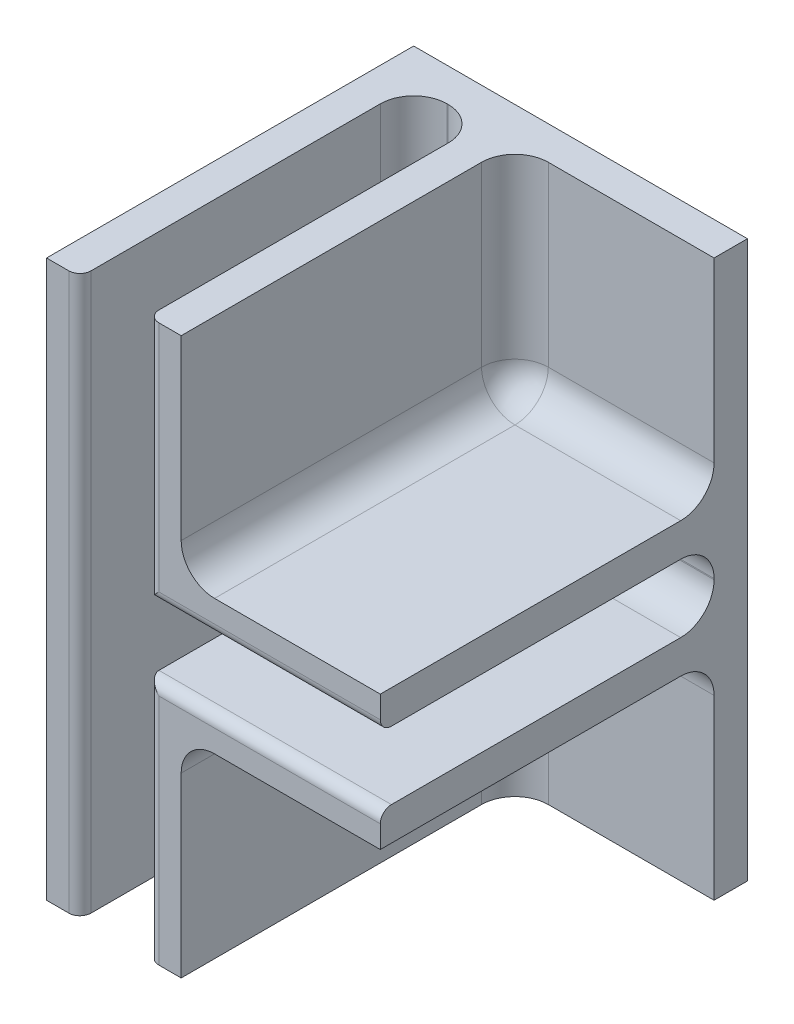
SolidWorks part; units mm, degrees
ref_plane "Front" through (0, 0, 0) normal (0, 0, 1) x (1, 0, 0)
ref_plane "Top" through (0, 0, 0) normal (0, 1, 0) x (1, 0, 0)
ref_plane "Right" through (0, 0, 0) normal (1, 0, 0) x (0, 0, -1)
sketch "Sketch1" plane through (0, 0, 0) normal (0, 0, 1) x (1, 0, 0)
  line L5 (0, 0) -> (30, 0)
  line L6 (0, 0) -> (0, 50)
  line L7 (0, 50) -> (30, 50)
  line L8 (30, 0) -> (30, 50)
  dimension "D1" = 50
  dimension "D2" = 30
extrude "Boss-Extrude1" add sketch "Sketch1" along normal blind 3
sketch "Sketch2" plane through (0, 0, 3) normal (0, 0, 1) x (1, 0, 0)
  line L0 (9.1, 50) -> (9.1, 28.05)
  line L25 (0, 50) -> (3, 50)
  line L26 (0, 50) -> (0, 0)
  line L27 (0, 0) -> (3, 0)
  line L28 (3, 50) -> (3, 0)
  line L29 (0, 0) -> (30, 0) construction
  line L48 (30, 50) -> (0, 50) construction
  line L50 (9.1, 28.05) -> (30, 28.05)
  line L51 (30, 0) -> (30, 50) construction
  line L52 (9.1, 0) -> (9.1, 21.95)
  line L53 (9.1, 21.95) -> (30, 21.95)
  line L54 (9.1, 50) -> (12.1, 50)
  line L55 (12.1, 50) -> (12.1, 31.05)
  line L56 (12.1, 31.05) -> (30, 31.05)
  line L57 (30, 31.05) -> (30, 28.05)
  line L58 (12.1, 0) -> (12.1, 18.95)
  line L59 (12.1, 18.95) -> (30, 18.95)
  line L60 (9.1, 0) -> (12.1, 0)
  line L61 (30, 18.95) -> (30, 21.95)
  dimension "D1" = 6.1
  dimension "D2" = 3
  dimension "D3" = 6.1
extrude "Boss-Extrude2" add sketch "Sketch2" along normal blind 30
fillet "Fillet2" radius 3 11 edges at (12.1, 18.95, 18) (21.05, 18.95, 3) (12.1, 9.475, 3) (12.1, 31.05, 18) (21.05, 31.05, 3) (12.1, 40.525, 3) (19.55, 21.95, 3) (19.55, 28.05, 3) (9.1, 39.025, 3) (9.1, 10.975, 3) (3, 25, 3)
fillet "Fillet3" radius 1 5 edges at (19.55, 21.95, 33) (19.55, 28.05, 33) (9.1, 39.025, 33) (9.1, 10.975, 33) (3, 25, 33)
